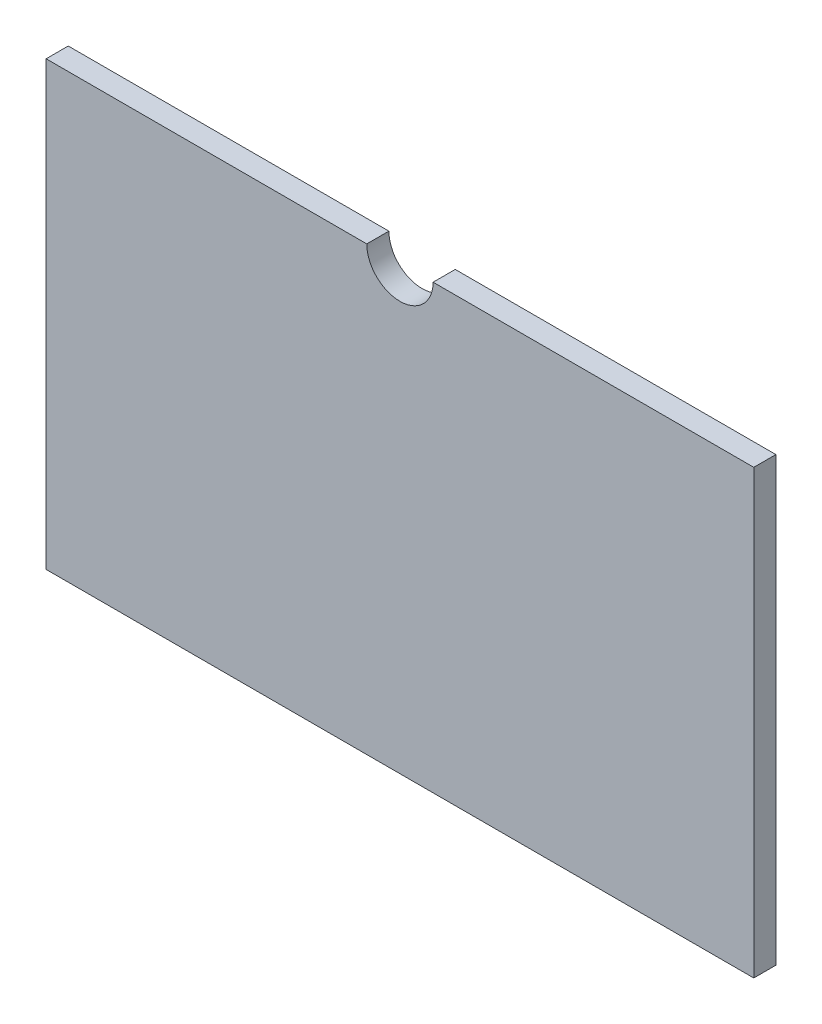
SolidWorks part; units mm, degrees
ref_plane "Front Plane" through (0, 0, 0) normal (0, 0, 1) x (1, 0, 0)
ref_plane "Top Plane" through (0, 0, 0) normal (0, 1, 0) x (1, 0, 0)
ref_plane "Right Plane" through (0, 0, 0) normal (1, 0, 0) x (0, 0, -1)
sketch "Sketch1" plane through (0, 0, 0) normal (0, 0, 1) x (1, 0, 0)
  line L0 (0, 0) -> (0, 100) construction
  line L1 (-160, 100) -> (-15, 100)
  line L2 (-160, 100) -> (-160, -100)
  line L3 (-160, -100) -> (160, -100)
  line L4 (160, 100) -> (160, -100)
  line L5 (-160, 0) -> (160, 0) construction
  line L6 (15, 100) -> (160, 100)
  line L7 (-15, 100) -> (15, 100) construction
  arc A0 (15, 100) -> (-15, 100) centre (0, 100) cw
  dimension "D3" = 15
  dimension "D1" = 320
  dimension "D2" = 200
  dimension "D4" = 160
extrude "Bottom Center Casing" add sketch "Sketch1" along normal blind 10
sketch "Sketch2" plane through (0, 0, 10) normal (0, 0, 1) x (1, 0, 0)
  line L0 (-15, 100) -> (-160, 100) construction
  line L1 (160, 100) -> (15, 100) construction
  line L2 (0, 100) -> (0, 66.7) construction
  line L3 (-87.5, 100) -> (87.5, 100) construction
  point P0 (-87.5, 100)
  point P3 (-87.5, 100)
  point P4 (87.5, 100)
  point P7 (87.5, 100)
  point P12 (0, 100)
  point P13 (0, 100)
  dimension "D1" = 33.3
